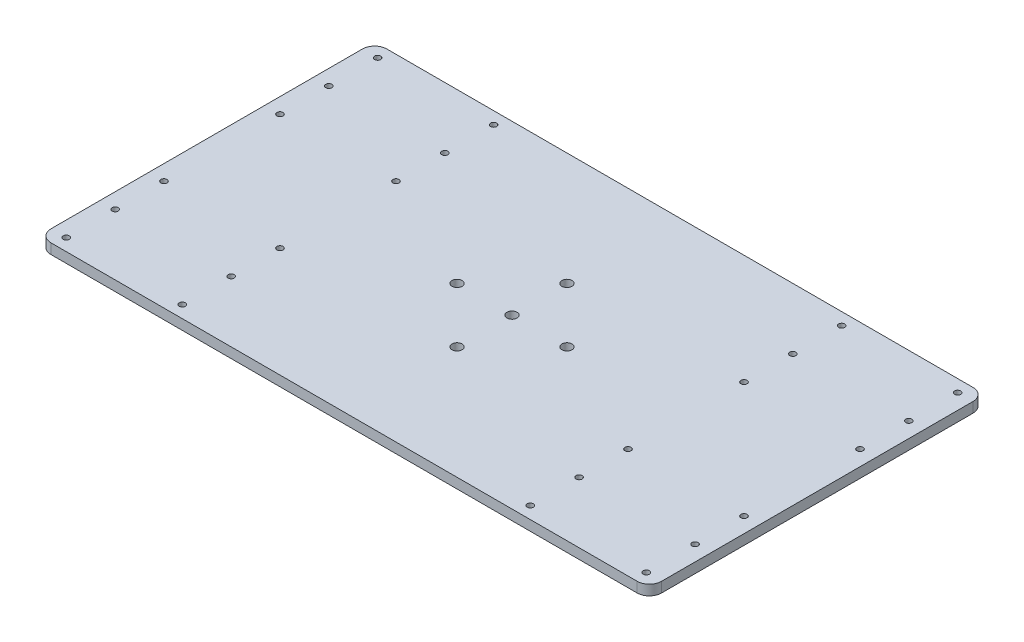
SolidWorks part; units mm, degrees
ref_plane "Front Plane" through (0, 0, 0) normal (0, 0, 1) x (1, 0, 0)
ref_plane "Top Plane" through (0, 0, 0) normal (0, 1, 0) x (1, 0, 0)
ref_plane "Right Plane" through (0, 0, 0) normal (1, 0, 0) x (0, 0, -1)
sketch "Sketch1" plane through (0, 0, 0) normal (0, 1, 0) x (1, 0, 0)
  line L0 (-142.5, 82.5) -> (-142.5, -82.5) construction
  line L1 (-144, -82.5) -> (144, -82.5)
  line L2 (-150, -76.5) -> (-150, 76.5)
  line L3 (-144, 82.5) -> (144, 82.5)
  line L4 (150, -76.5) -> (150, 76.5)
  line L5 (-150, -82.5) -> (150, 82.5) construction
  line L6 (-150, 82.5) -> (150, -82.5) construction
  line L7 (0, 0) -> (-30, -30) construction
  line L8 (0, 82.5) -> (0, -82.5) construction
  line L9 (-150, 0) -> (150, 0) construction
  line L10 (-9.5, -10) -> (9.5, -10) construction
  line L11 (-10, -9.5) -> (-10, 9.5) construction
  line L12 (-9.5, 10) -> (9.5, 10) construction
  line L13 (10, -9.5) -> (10, 9.5) construction
  line L14 (-10, -10) -> (10, 10) construction
  line L15 (-10, 10) -> (10, -10) construction
  circle A0 centre (-142.5, 76.5) radius 1.5
  circle A1 centre (-142.5, 52.5) radius 1.5
  circle A2 centre (-142.5, 28.5) radius 1.5
  circle A3 centre (-85.5, 76.5) radius 1.5
  circle A4 centre (-85.5, 52.5) radius 1.5
  circle A5 centre (-85.5, 28.5) radius 1.5
  circle A6 centre (85.5, 28.5) radius 1.5
  circle A7 centre (85.5, 52.5) radius 1.5
  circle A8 centre (85.5, 76.5) radius 1.5
  circle A9 centre (142.5, 28.5) radius 1.5
  circle A10 centre (142.5, 52.5) radius 1.5
  circle A11 centre (142.5, 76.5) radius 1.5
  circle A12 centre (142.5, -76.5) radius 1.5
  circle A13 centre (142.5, -52.5) radius 1.5
  circle A14 centre (142.5, -28.5) radius 1.5
  circle A15 centre (85.5, -76.5) radius 1.5
  circle A16 centre (85.5, -52.5) radius 1.5
  circle A17 centre (85.5, -28.5) radius 1.5
  circle A18 centre (-85.5, -28.5) radius 1.5
  circle A19 centre (-85.5, -52.5) radius 1.5
  circle A20 centre (-85.5, -76.5) radius 1.5
  circle A21 centre (-142.5, -28.5) radius 1.5
  circle A22 centre (-142.5, -52.5) radius 1.5
  circle A23 centre (-142.5, -76.5) radius 1.5
  arc A24 (9.5, 10) -> (10, 9.5) centre (9.5, 9.5) cw construction
  arc A25 (10, -9.5) -> (9.5, -10) centre (9.5, -9.5) cw construction
  arc A26 (-9.5, -10) -> (-10, -9.5) centre (-9.5, -9.5) cw construction
  arc A27 (-10, 9.5) -> (-9.5, 10) centre (-9.5, 9.5) cw construction
  circle A28 centre (0, 27) radius 2.5
  circle A29 centre (27, 0) radius 2.5
  circle A30 centre (0, -27) radius 2.5
  circle A31 centre (-27, 0) radius 2.5
  circle A32 centre (0, 0) radius 2.5
  circle A33 centre (-30, -30) radius 2.5 construction
  circle A34 centre (-30, 30) radius 2.5 construction
  circle A35 centre (30, 30) radius 2.5 construction
  circle A36 centre (30, -30) radius 2.5 construction
  arc A37 (144, 82.5) -> (150, 76.5) centre (144, 76.5) cw
  arc A38 (150, -76.5) -> (144, -82.5) centre (144, -76.5) cw
  arc A39 (-144, -82.5) -> (-150, -76.5) centre (-144, -76.5) cw
  arc A40 (-150, 76.5) -> (-144, 82.5) centre (-144, 76.5) cw
  point P0 (0, 0)
  point P59 (0, 0)
  point P88 (0, 0)
  point P98 (0, 0)
  dimension "D5" = 3
  dimension "D9" = 0.5
  dimension "D10" = 17
  dimension "D11" = 5
  dimension "D14" = 57
  dimension "D15" = 45
  dimension "D17" = 60
  dimension "D18" = 5
  dimension "D19" = 6
  dimension "D1" = 300
  dimension "D2" = 165
  dimension "D3" = 7.5
  dimension "D4" = 3
  dimension "D6" = 6
  dimension "D8" = 20
  dimension "D13" = 24
  dimension "D7" = 2
  dimension "D12" = 4
  dimension "D16" = 4
extrude "Boss-Extrude1" add sketch "Sketch1" along normal blind 5
